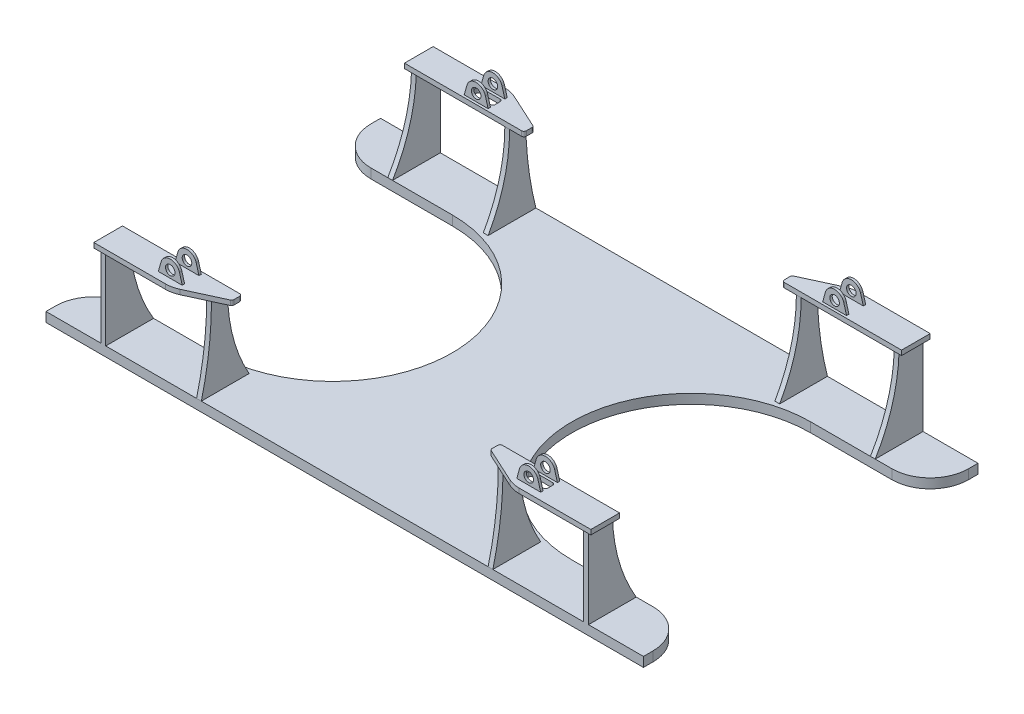
SolidWorks part; units mm, degrees
material "fiber.c"
ref_plane "Front Plane" through (0, 0, 0) normal (0, 0, 1) x (1, 0, 0)
ref_plane "Top Plane" through (0, 0, 0) normal (0, 1, 0) x (1, 0, 0)
ref_plane "Right Plane" through (0, 0, 0) normal (1, 0, 0) x (0, 0, -1)
sketch "Sketch2" plane through (0, 0, 0) normal (0, 1, 0) x (1, 0, 0)
  line L0 (-272.5, 125) -> (-187.5, 125)
  line L1 (312.5, -175) -> (-312.5, -175)
  line L2 (312.5, -175) -> (312.5, -165)
  line L3 (312.5, 175) -> (-312.5, 175)
  line L4 (-312.5, -175) -> (-312.5, -165)
  line L5 (312.5, -175) -> (-312.5, 175) construction
  line L6 (312.5, 175) -> (-312.5, -175) construction
  line L7 (-272.5, -125) -> (-187.5, -125)
  line L8 (0, 200.5165) -> (0, -225.3099) construction
  line L9 (-312.5, 0) -> (-62.5, 0) construction
  line L10 (312.5, 0) -> (62.5, 0) construction
  line L11 (-312.5, 165) -> (-312.5, 175)
  line L12 (187.5, -125) -> (272.5, -125)
  line L13 (312.5, 165) -> (312.5, 175)
  line L14 (187.5, 125) -> (272.5, 125)
  arc A0 (-187.5, -125) -> (-187.5, 125) centre (-187.5, 0) ccw
  arc A1 (187.5, 125) -> (187.5, -125) centre (187.5, 0) ccw
  arc A2 (-272.5, -125) -> (-312.5, -165) centre (-272.5, -165) ccw
  arc A3 (-272.5, 125) -> (-312.5, 165) centre (-272.5, 165) cw
  arc A4 (312.5, -165) -> (272.5, -125) centre (272.5, -165) ccw
  arc A5 (272.5, 125) -> (312.5, 165) centre (272.5, 165) ccw
  point P0 (0, 0)
  point P30 (-312.5, 125)
  point P35 (312.5, 125)
  dimension "D7" = 40
  dimension "D1" = 625
  dimension "D2" = 350
  dimension "D3" = 50
  dimension "D4" = 50
  dimension "D5" = 250
  dimension "D6" = 250
extrude "Boss-Extrude1" add sketch "Sketch2" along normal mid plane 10
sketch "Sketch5" plane through (0, 0, 0) normal (1, 0, 0) x (0, 0, -1)
  line L0 (175, 5) -> (125, 5)
  line L1 (175, 5) -> (175, 95)
  line L2 (175, 95) -> (150, 95)
  arc A0 (150, 95) -> (125, 5) centre (-24.5, 95) cw
  dimension "D1" = 90
  dimension "D2" = 25
extrude "Boss-Extrude2" add sketch "Sketch5" along normal blind 5 from offset 250
sketch "Sketch7" plane through (0, 95, 0) normal (0, 1, 0) x (1, 0, 0)
  line L0 (260, 147.5) -> (137.5, 147.5)
  line L1 (135, 150) -> (135, 155.899)
  line L2 (260, 147.5) -> (260, 177.5)
  line L3 (260, 177.5) -> (185, 177.5)
  line L4 (250, 175) -> (-312.5, 175) construction
  line L5 (172.4497, 174.7487) -> (136.4541, 158.1698)
  line L6 (255, 175) -> (255, 150) construction
  line L7 (255, 150) -> (250, 150) construction
  line L8 (255, 175) -> (250, 175) construction
  arc A0 (137.5, 147.5) -> (135, 150) centre (137.5, 150) cw
  arc A1 (135, 155.899) -> (136.4541, 158.1698) centre (137.5, 155.899) cw
  arc A2 (185, 177.5) -> (172.4497, 174.7487) centre (185, 147.5) ccw
  point P11 (135, 147.5)
  point P14 (135, 157.5)
  point P17 (170.0347, 175)
  point P19 (252.5, 175)
  dimension "D4" = 2.5
  dimension "D5" = 30
  dimension "D1" = 125
  dimension "D2" = 90
  dimension "D3" = 10
  dimension "D6" = 5
  dimension "D7" = 2.5
  dimension "D8" = 2.5
  dimension "D9" = 75
extrude "Boss-Extrude3" add sketch "Sketch7" against normal blind 5
ref_plane "Plane1" through (150, 0, 0) normal (-1, 0, 0) x (0, 0, 1)
sketch "Sketch10" plane through (150, 0, 0) normal (-1, 0, 0) x (0, 0, 1)
  line L0 (-175, 5) -> (-125, 5)
  line L1 (-164.4087, 90) -> (-147.5, 90)
  line L4 (-174.7487, 90) -> (-158.1698, 90) construction
  arc A0 (-164.4087, 90) -> (-175, 5) centre (-510.7873, 90) cw
  arc A1 (-147.5, 90) -> (-125, 5) centre (24.3056, 90) ccw
extrude "Boss-Extrude4" add sketch "Sketch10" against normal blind 5
ref_point "Point1"
sketch "Sketch11" plane through (0, 95, 0) normal (0, 1, 0) x (1, 0, 0)
  line L0 (187.5, 217.7132) -> (187.5, -220.2998) construction
sketch "Sketch12" plane through (0, 0, -147.5) normal (0, 0, 1) x (1, 0, 0)
  line L0 (187.5, 95) -> (187.5, 102.5) construction
  line L1 (137.5, 95) -> (260, 95) construction
  line L2 (175, 95) -> (200, 95)
  line L3 (175, 95) -> (177.8741, 105.2098)
  line L4 (200, 95) -> (197.1259, 105.2098)
  circle A0 centre (187.5, 102.5) radius 5
  arc A1 (197.1259, 105.2098) -> (177.8741, 105.2098) centre (187.5, 102.5) ccw
  point P6 (187.5, 95)
  dimension "D3" = 20
  dimension "D4" = 10
  dimension "D1" = 7.5
  dimension "D2" = 25
extrude "Boss-Extrude5" add sketch "Sketch12" against normal blind 2.5 from offset 2.5 offset against normal yes
extrude "Boss-Extrude6" add sketch "Sketch12<2>" against normal blind 2.5 from offset 20 offset against normal yes
sketch "Sketch12<2>" plane through (0, 0, -147.5) normal (0, 0, 1) x (1, 0, 0) same geometry as "Sketch12"
mirror "Mirror1" about plane through (0, 0, 0) normal (0, 0, 1) of "Boss-Extrude5", "Boss-Extrude2", "Boss-Extrude3", "Boss-Extrude4", "Boss-Extrude6"
mirror "Mirror2" about plane through (0, 0, 0) normal (1, 0, 0) of "Mirror1"
sketch "Sketch13" plane through (0, 95, 0) normal (0, 1, 0) x (1, 0, 0)
  line L0 (175, -152.5) -> (200, -152.5) construction
  line L1 (175, -155) -> (200, -155)
  line L2 (175, -155) -> (175, -165)
  line L3 (175, -165) -> (200, -165)
  line L4 (200, -155) -> (200, -165)
  line L5 (175, -155) -> (200, -165) construction
  line L6 (175, -165) -> (200, -155) construction
  point P0 (187.5, -160)
  point P8 (187.5, -152.5)
  dimension "D1" = 25
  dimension "D2" = 10
  dimension "D3" = 2.5
extrude "Cut-Extrude1" cut sketch "Sketch13" against normal up to vertex (5 mm away) up to point (260, 90, 177.5)
fillet "Fillet1" radius 2.5 4 edges at (175, 92.5, 165) (200, 92.5, 165) (200, 92.5, 155) (175, 92.5, 155)
sketch "Sketch15" plane through (0, 95, 0) normal (0, 1, 0) x (1, 0, 0)
  line L0 (-175, 167.5) -> (-200, 167.5) construction
  line L1 (-175, 155) -> (-200, 155)
  line L2 (-175, 155) -> (-175, 165)
  line L3 (-175, 165) -> (-200, 165)
  line L4 (-200, 155) -> (-200, 165)
  line L5 (-175, 155) -> (-200, 165) construction
  line L6 (-175, 165) -> (-200, 155) construction
  line L7 (-175, 152.5) -> (-200, 152.5) construction
  point P0 (-187.5, 160)
  point P10 (-187.5, 152.5)
  dimension "D1" = 2.5
  dimension "D2" = 10
  dimension "D3" = 25
extrude "Cut-Extrude2" cut sketch "Sketch15" against normal up to vertex (5 mm away) up to point (-260, 90, -147.5)
fillet "Fillet2" radius 2.5 4 edges at (-175, 92.5, -155) (-200, 92.5, -155) (-175, 92.5, -165) (-200, 92.5, -165)
